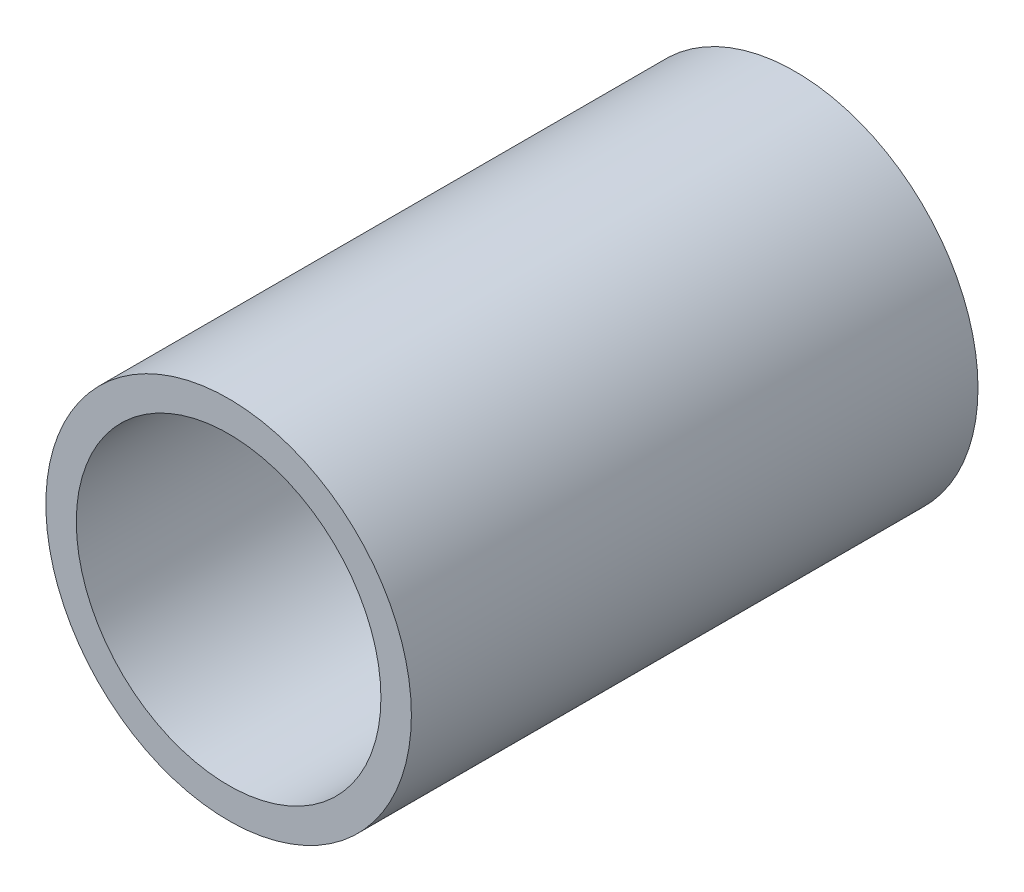
SolidWorks part; units mm, degrees
material "PLA 50%"
ref_plane "Front Plane" through (0, 0, 0) normal (0, 0, 1) x (1, 0, 0)
ref_plane "Top Plane" through (0, 0, 0) normal (0, 1, 0) x (1, 0, 0)
ref_plane "Right Plane" through (0, 0, 0) normal (1, 0, 0) x (0, 0, -1)
ref_axis "X" through (-88.99, 0, 0) along (1, 0, 0)
ref_axis "Y" through (0, 55, 0) along (0, -1, 0)
ref_axis "Z" through (0, 0, -88.99) along (0, 0, 1)
sketch "Sketch1" plane through (0, 0, 0) normal (0, 0, 1) x (1, 0, 0)
  circle A0 centre (0, 0) radius 5
  circle A1 centre (0, 0) radius 6
  dimension "D1" = 10
  dimension "D2" = 12
extrude "Boss-Extrude1" add sketch "Sketch1" against normal up to surface (18.6012 mm away)
